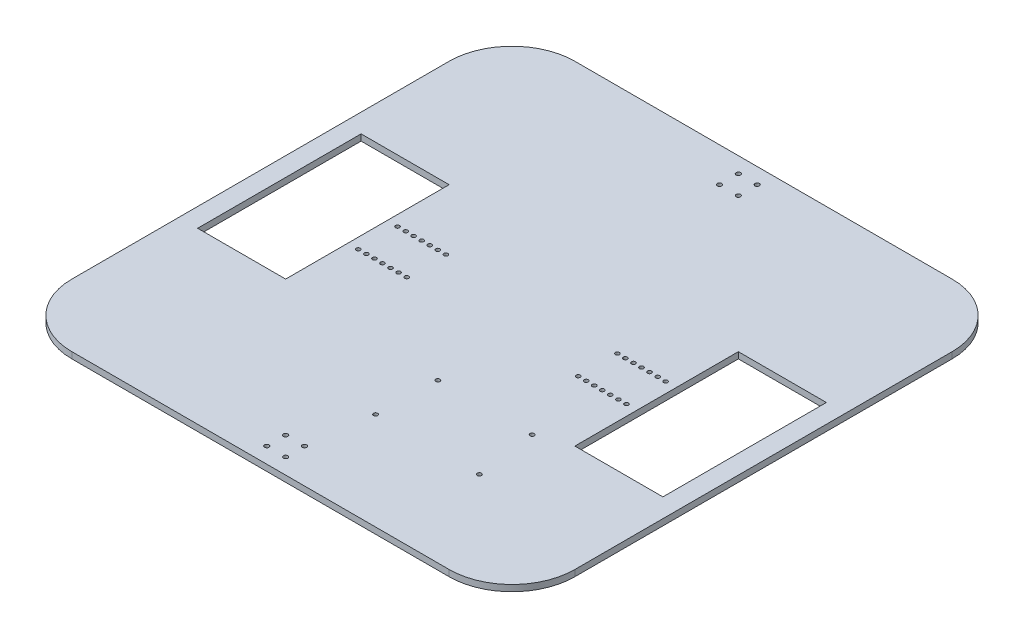
SolidWorks part; units mm, degrees
ref_plane "Front Plane" through (0, 0, 0) normal (0, 0, 1) x (1, 0, 0)
ref_plane "Top Plane" through (0, 0, 0) normal (0, 1, 0) x (1, 0, 0)
ref_plane "Right Plane" through (0, 0, 0) normal (1, 0, 0) x (0, 0, -1)
sketch "Sketch1" plane through (0, 0, 0) normal (0, 1, 0) x (1, 0, 0)
  line L0 (0, -1000) -> (0, 49000) construction
  line L1 (-185, 65) -> (-115, 65)
  line L2 (-185, 65) -> (-185, -65)
  line L3 (-185, -65) -> (-115, -65)
  line L4 (-115, 65) -> (-115, -65)
  line L5 (185, -65) -> (115, -65)
  line L6 (115, 65) -> (115, -65)
  line L7 (185, 65) -> (115, 65)
  line L8 (185, 65) -> (185, -65)
  line L9 (-1000, 0) -> (49000, 0) construction
  line L10 (-10, 190) -> (10, 190)
  line L11 (-10, 190) -> (-10, 170)
  line L12 (-10, 170) -> (10, 170)
  line L13 (10, 190) -> (10, 170)
  line L14 (-1010, 180) -> (48990, 180) construction
  line L15 (-1010, -180) -> (48990, -180) construction
  line L16 (0, 1000) -> (0, -49000) construction
  line L17 (-10, -170) -> (10, -170)
  line L18 (10, -190) -> (10, -170)
  line L19 (-10, -190) -> (10, -190)
  line L20 (-10, -190) -> (-10, -170)
  line L22 (-200, 200) -> (200, 200)
  line L23 (-200, 200) -> (-200, -200)
  line L24 (-200, -200) -> (200, -200)
  line L25 (200, 200) -> (200, -200)
  circle A0 centre (0, 0) radius 200 construction
  circle A1 centre (-7.5, 187.5) radius 1.75
  circle A2 centre (7.5, 187.5) radius 1.75
  circle A3 centre (7.5, 172.5) radius 1.75
  circle A4 centre (-7.5, 172.5) radius 1.75
  circle A5 centre (7.5, -187.5) radius 1.75
  circle A6 centre (-7.5, -187.5) radius 1.75
  circle A7 centre (-7.5, -172.5) radius 1.75
  circle A8 centre (7.5, -172.5) radius 1.75
  point P7 (-115, 0)
  point P8 (-150, 65)
  point P19 (0, 190)
  point P22 (-10, 180)
  dimension "D1" = 400
  dimension "D7" = 3.5
  dimension "D2" = 70
  dimension "D3" = 130
  dimension "D4" = 150
  dimension "D5" = 20
  dimension "D6" = 180
  dimension "D8" = 2.5
  dimension "D9" = 2.5
extrude "Boss-Extrude2" add sketch "Sketch1" along normal blind 5 contours L25 L22 L23 L24 L1 L4 L3 L2 L7 L8 L5 L6 L10 L13 L12 L11 L19 L20 L17 L18 | L20 L19 L18 L17 A6 A5 A7 A8 | L13 L10 L11 L12 A2 A1 A3 A4 region at (0, 0, -180) region at (0, 0, 180) region at (0, 0, 0)
fillet "Fillet1" radius 50 4 edges at (200, 2.5, -200) (200, 2.5, 200) (-200, 2.5, 200) (-200, 2.5, -200)
sketch "Sketch2" plane through (0, 5, 0) normal (0, 1, 0) x (1, 0, 0)
  line L0 (-1094.0419, 0) -> (48905.9581, 0) construction
  line L1 (-115, 18.8) -> (-63.5, 18.8) construction
  line L2 (-115, 18.8) -> (-115, -18.8) construction
  line L3 (-115, -18.8) -> (-63.5, -18.8) construction
  line L4 (-63.5, 18.8) -> (-63.5, -18.8) construction
  line L5 (-115, 65) -> (-115, -65) construction
  line L6 (-185, 65) -> (-185, -65) construction
  line L7 (0, -1000) -> (0, 49000) construction
  line L8 (115, -18.8) -> (63.5, -18.8) construction
  line L9 (63.5, 18.8) -> (63.5, -18.8) construction
  line L10 (115, 18.8) -> (63.5, 18.8) construction
  line L11 (115, 18.8) -> (115, -18.8) construction
  circle A0 centre (-106.6, 15.6) radius 1.6
  circle A1 centre (-100.2, 15.6) radius 1.6
  circle A2 centre (-93.8, 15.6) radius 1.6
  circle A3 centre (-87.4, 15.6) radius 1.6
  circle A4 centre (-81, 15.6) radius 1.6
  circle A5 centre (-74.6, 15.6) radius 1.6
  circle A6 centre (-68.2, 15.6) radius 1.6
  circle A7 centre (-68.2, -15.6) radius 1.6
  circle A8 centre (-74.6, -15.6) radius 1.6
  circle A9 centre (-81, -15.6) radius 1.6
  circle A10 centre (-87.4, -15.6) radius 1.6
  circle A11 centre (-93.8, -15.6) radius 1.6
  circle A12 centre (-100.2, -15.6) radius 1.6
  circle A13 centre (-106.6, -15.6) radius 1.6
  circle A14 centre (68.2, -15.6) radius 1.6
  circle A15 centre (74.6, -15.6) radius 1.6
  circle A16 centre (81, -15.6) radius 1.6
  circle A17 centre (87.4, -15.6) radius 1.6
  circle A18 centre (93.8, -15.6) radius 1.6
  circle A19 centre (100.2, -15.6) radius 1.6
  circle A20 centre (106.6, -15.6) radius 1.6
  circle A21 centre (68.2, 15.6) radius 1.6
  circle A22 centre (74.6, 15.6) radius 1.6
  circle A23 centre (81, 15.6) radius 1.6
  circle A24 centre (87.4, 15.6) radius 1.6
  circle A25 centre (93.8, 15.6) radius 1.6
  circle A26 centre (100.2, 15.6) radius 1.6
  circle A27 centre (106.6, 15.6) radius 1.6
  point P9 (-115, 0)
  point P40 (-185, 0)
  dimension "D3" = 3.2
  dimension "D7" = 6.4
  dimension "D5" = 8.4
  dimension "D1" = 37.6
  dimension "D2" = 4.7
  dimension "D4" = 31.2
  dimension "D6" = 7
extrude "Cut-Extrude1" cut sketch "Sketch2" against normal blind 5
sketch "Sketch3" plane through (0, 5, 0) normal (0, 1, 0) x (1, 0, 0)
  line L0 (-150, -200) -> (150, -200) construction
  line L1 (0, -71.66) -> (101.6, -71.66) construction
  line L2 (0, -71.66) -> (0, -125) construction
  line L3 (0, -125) -> (101.6, -125) construction
  line L4 (101.6, -71.66) -> (101.6, -125) construction
  line L5 (-200, 150) -> (-200, -150) construction
  circle A0 centre (13.97, -122.46) radius 1.65
  circle A1 centre (15.24, -74.2) radius 1.65
  circle A2 centre (96.52, -122.46) radius 1.65
  circle A3 centre (90.17, -74.2) radius 1.65
  point P9 (0, -98.33)
  point P11 (0, 0)
  dimension "D5" = 3.3
  dimension "D8" = 3.3
  dimension "D9" = 96.52
  dimension "D10" = 90.17
  dimension "D1" = 101.6
  dimension "D2" = 53.34
  dimension "D3" = 13.97
  dimension "D4" = 2.54
  dimension "D6" = 15.24
  dimension "D7" = 50.8
  dimension "D11" = 75
  dimension "D12" = 200
extrude "Cut-Extrude2" cut sketch "Sketch3" against normal blind 10 contours A1 | A2 | L2 L1 L4 L3 | A0 | A3 region at (15.24, 5, 74.2) region at (96.52, 5, 122.46)
